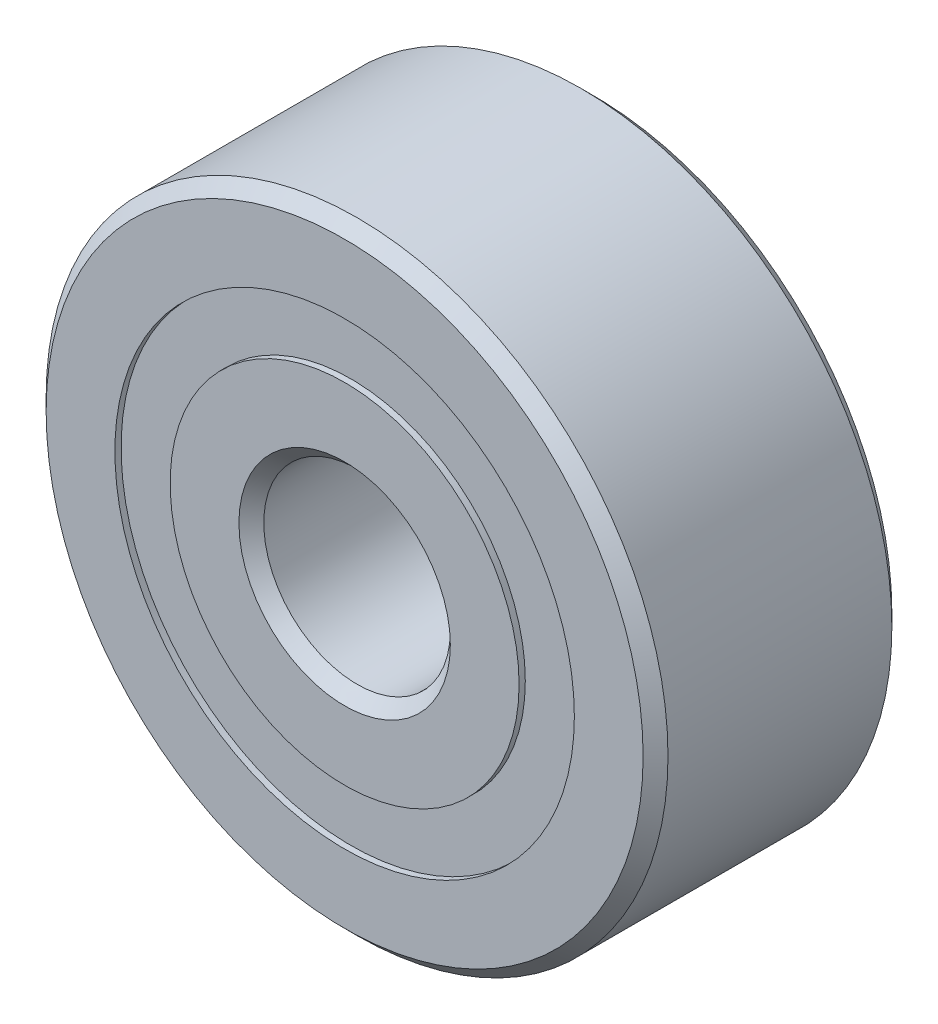
SolidWorks part; units mm, degrees
ref_plane "Front Plane" through (0, 0, 0) normal (0, 0, 1) x (1, 0, 0)
ref_plane "Top Plane" through (0, 0, 0) normal (0, 1, 0) x (1, 0, 0)
ref_plane "Right Plane" through (0, 0, 0) normal (1, 0, 0) x (0, 0, -1)
sketch "Sketch1" plane through (0, 0, 0) normal (1, 0, 0) x (0, 0, -1)
  line L0 (-2, 0) -> (2, 0) construction
  line L1 (0, 5) -> (0, -5) construction
  line L2 (1.8, 5) -> (-1.8, 5)
  line L3 (-1.8, 5) -> (-2, 4.8)
  line L4 (-2, 4.8) -> (-2, 3.6944)
  line L5 (-2, 3.6944) -> (-0.8889, 3.6944)
  line L6 (2, 3.6944) -> (0.8889, 3.6944)
  line L7 (2, 4.8) -> (2, 3.6944)
  line L8 (1.8, 5) -> (2, 4.8)
  line L9 (0, 5) -> (0, 3.25) construction
  line L10 (0, 3.25) -> (0, 1.5) construction
  arc A0 (-0.8889, 3.6944) -> (0.8889, 3.6944) centre (0, 3.25) cw
  arc A1 (-0.8889, 3.6944) -> (0.8889, 3.6944) centre (0, 3.25) ccw construction
  point P14 (0, 1.5)
  point P15 (0, -1.5)
  dimension "Width" = 4
  dimension "OD" = 10
  dimension "D1" = 45
  dimension "D2" = 0.2
  dimension "D3" = 1.7778
  dimension "Shaft Dia" = 3
  dimension "D4" = 0.4444
revolve "Revolve1" add sketch "Sketch1" angle 360 about L0
sketch "Sketch2" plane through (0, 0, 0) normal (1, 0, 0) x (0, 0, -1)
  line L0 (-2, 2.8056) -> (-0.8889, 2.8056)
  line L1 (-2, 4.8) -> (-2, -4.8) construction
  line L2 (-2, 2.8056) -> (-2, 1.7)
  line L3 (-2, 1.7) -> (-1.8, 1.5)
  line L4 (-1.8, 1.5) -> (1.8, 1.5)
  line L5 (0, 5) -> (0, -5) construction
  line L6 (0, 1.5) -> (0, 2.2562) construction
  line L7 (0, 2.2562) -> (0, 1.5) construction
  line L8 (-2, 2.8056) -> (-2, 0.5944) construction
  line L10 (2, 2.8056) -> (0.8889, 2.8056)
  line L11 (2, 2.8056) -> (2, 1.7)
  line L12 (2, 1.7) -> (1.8, 1.5)
  arc A0 (-0.8889, 2.8056) -> (0.8889, 2.8056) centre (0, 3.25) ccw
  arc A1 (0.8889, 3.6944) -> (-0.8889, 3.6944) centre (0, 3.25) ccw construction
  circle A2 centre (0, 3.25) radius 0.9938 construction
  dimension "D1" = 0.2
  dimension "D2" = 45
revolve "Revolve2" add sketch "Sketch2" angle 360 about L0
sketch "Sketch3" plane through (0, 0, 0) normal (1, 0, 0) x (0, 0, -1)
  line L0 (-0.9938, 3.25) -> (0.9938, 3.25)
  line L1 (0, 3.25) -> (0, 0) construction
  circle A1 centre (0, 3.25) radius 0.9938 construction
  arc A2 (-0.9938, 3.25) -> (0.9938, 3.25) centre (0, 3.25) cw
  arc A3 (0.8889, 3.6944) -> (-0.8889, 3.6944) centre (0, 3.25) ccw construction
  dimension "D1" = 1.9876
  dimension "D2" = 3.25
revolve "Revolve3" add sketch "Sketch3" angle 360 about L0
ref_axis "Axis1" through (0, 0, -2) along (0, 0, 1)
pattern_circular "CirPattern1" count 9 every 40 about axis through (0, 0, -2) along (0, 0, 1) of bodies 104
sketch "Sketch5" plane through (0, 0, 0) normal (1, 0, 0) x (0, 0, -1)
  line L0 (-2, 2.8056) -> (-0.8889, 2.8056) construction
  line L1 (-1.9, 3.6944) -> (-0.9938, 3.6944)
  line L2 (-1.9, 3.6944) -> (-1.9, 2.8056)
  line L3 (-1.9, 2.8056) -> (-0.9938, 2.8056)
  line L4 (-0.9938, 3.6944) -> (-0.9938, 2.8056)
  line L5 (0.9938, 3.6944) -> (1.9, 3.6944)
  line L6 (0.9938, 3.6944) -> (0.9938, 2.8056)
  line L7 (0.9938, 2.8056) -> (1.9, 2.8056)
  line L8 (1.9, 3.6944) -> (1.9, 2.8056)
  line L9 (-2, 3.6944) -> (-0.8889, 3.6944) construction
  line L10 (-1.9, 4.9) -> (-1.9, 3.6944) construction
  line L11 (-1.8, 5) -> (-2, 4.8) construction
  circle A0 centre (0, 3.25) radius 0.9938 construction
revolve "Revolve5" add sketch "Sketch5" angle 360 about L0
sketch "Sketch6" plane through (0, 0, 0) normal (0, 1, 0) x (1, 0, 0)
  point P0 (5, -2)
  point P1 (5, 2)
ref_axis "Center Axis 1" through (0, 0, -2.4268) along (0, 0, 1)
ref_plane "Contact Plane 1" through (0, 0, 2) normal (0, 0, 1) x (1, 0, 0)
ref_plane "Contact Plane 2" through (0, 0, -2) normal (0, 0, -1) x (-1, 0, 0)
equation "\"D2@Sketch1\" = \"Width@Sketch1\"*.05"
equation "\"D3@Sketch1\" = \"Width@Sketch1\"/2.25"
equation "\"D4@Sketch1\" = \"D3@Sketch1\"/4"
equation "\"Balls@CirPattern1\"=\"D2@Sketch3\"*2*pi/\"D1@Sketch3\"-1"
equation "\"D2@CirPattern1\" = 360/\"Balls@CirPattern1\""
equation "\"D1@Sketch2\"=\"D2@Sketch1\""
equation "\"D1@Sketch6\"=\"Width@Sketch1\""
